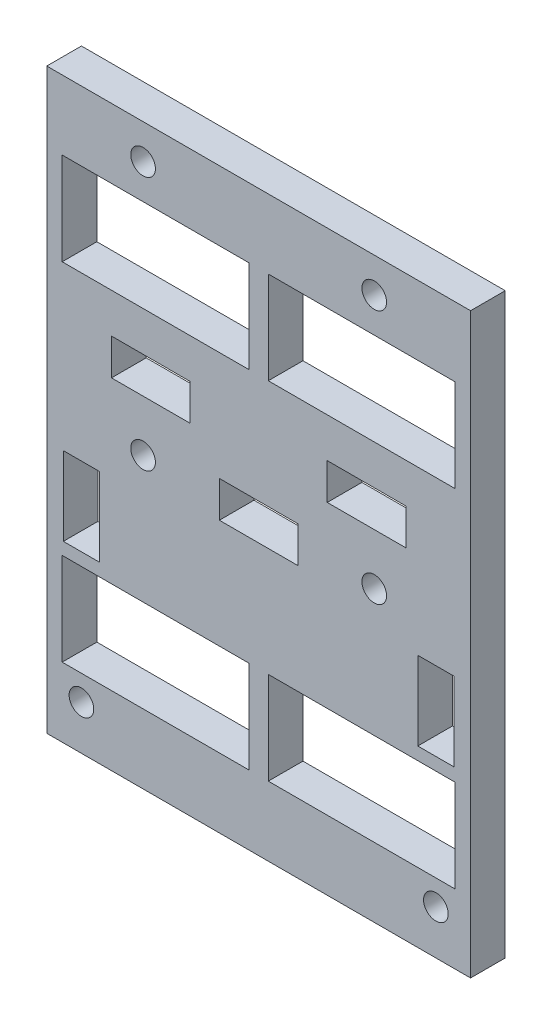
SolidWorks part; units mm, degrees
ref_plane "Front Plane" through (0, 0, 0) normal (0, 0, 1) x (1, 0, 0)
ref_plane "Top Plane" through (0, 0, 0) normal (0, 1, 0) x (1, 0, 0)
ref_plane "Right Plane" through (0, 0, 0) normal (1, 0, 0) x (0, 0, -1)
sketch "Sketch1" plane through (0, 0, 0) normal (0, 0, 1) x (1, 0, 0)
  line L0 (0, -37.5) -> (0, 37.5) construction
  line L1 (-27.5, -37.5) -> (27.5, -37.5)
  line L2 (-27.5, -37.5) -> (-27.5, 37.5)
  line L3 (-27.5, 37.5) -> (27.5, 37.5)
  line L4 (27.5, -37.5) -> (27.5, 37.5)
  line L5 (-27.5, -37.5) -> (27.5, 37.5) construction
  line L6 (-27.5, 37.5) -> (27.5, -37.5) construction
  line L7 (-27.5, 0) -> (27.5, 0) construction
  line L8 (-27.5, 22.5) -> (27.5, 22.5) construction
  line L9 (25.5, 16.5) -> (1.25, 28.5) construction
  line L10 (-25.5, 28.5) -> (-1.25, 28.5)
  line L11 (-25.5, 28.5) -> (-25.5, 16.5)
  line L12 (-25.5, 16.5) -> (-1.25, 16.5)
  line L13 (-1.25, 28.5) -> (-1.25, 16.5)
  line L14 (-25.5, 28.5) -> (-1.25, 16.5) construction
  line L15 (-25.5, 16.5) -> (-1.25, 28.5) construction
  line L16 (25.5, 28.5) -> (1.25, 16.5) construction
  line L17 (1.25, 28.5) -> (1.25, 16.5)
  line L18 (25.5, 16.5) -> (1.25, 16.5)
  line L19 (25.5, 28.5) -> (25.5, 16.5)
  line L20 (25.5, 28.5) -> (1.25, 28.5)
  line L21 (25.5, -28.5) -> (1.25, -16.5) construction
  line L22 (-25.5, -16.5) -> (-1.25, -28.5) construction
  line L23 (-25.5, -28.5) -> (-1.25, -16.5) construction
  line L24 (25.5, -16.5) -> (1.25, -28.5) construction
  line L25 (25.5, -28.5) -> (1.25, -28.5)
  line L26 (25.5, -28.5) -> (25.5, -16.5)
  line L27 (25.5, -16.5) -> (1.25, -16.5)
  line L28 (1.25, -28.5) -> (1.25, -16.5)
  line L29 (-1.25, -28.5) -> (-1.25, -16.5)
  line L30 (-25.5, -16.5) -> (-1.25, -16.5)
  line L31 (-25.5, -28.5) -> (-25.5, -16.5)
  line L32 (-25.5, -28.5) -> (-1.25, -28.5)
  point P0 (0, 0)
  point P12 (-13.375, 22.5)
  point P21 (13.375, 22.5)
  point P30 (13.375, -22.5)
  point P31 (-13.375, -22.5)
  dimension "D1" = 55
  dimension "D2" = 75
  dimension "D3" = 22.5
  dimension "D4" = 24.25
  dimension "D5" = 12
  dimension "D6" = 1.25
extrude "Boss-Extrude1" add sketch "Sketch1" along normal blind 4.5
sketch "Sketch2" plane through (0, 0, 4.5) normal (0, 0, 1) x (1, 0, 0)
  line L0 (0, -37.5) -> (0, 37.5) construction
  line L1 (-27.5, -37.5) -> (27.5, -37.5) construction
  line L2 (27.5, 37.5) -> (-27.5, 37.5) construction
  line L3 (-27.5, 0) -> (27.5, 0) construction
  line L4 (-27.5, 37.5) -> (-27.5, -37.5) construction
  line L5 (27.5, -37.5) -> (27.5, 37.5) construction
  line L6 (-15, 0) -> (15, 0) construction
  circle A0 centre (-15, 33) radius 1.6
  circle A1 centre (15, 33) radius 1.6
  circle A2 centre (15, 0) radius 1.6
  circle A3 centre (-15, 0) radius 1.6
  dimension "D1" = 3.2
  dimension "D7" = 3.2
  dimension "D8" = 3.2
  dimension "D2" = 15
  dimension "D3" = 33
  dimension "D4" = 30
  dimension "D5" = 15
  dimension "D6" = 0
extrude "screwHoles" cut sketch "Sketch2" against normal through all
sketch "Sketch3" plane through (0, 0, 4.5) normal (0, 0, 1) x (1, 0, 0)
  line L0 (-27.5, 9) -> (26.0486, 9) construction
  line L1 (-27.5, 37.5) -> (-27.5, -37.5) construction
  line L3 (0, 37.5) -> (0, -37.5) construction
  line L4 (27.5, 37.5) -> (-27.5, 37.5) construction
  line L5 (-27.5, -37.5) -> (27.5, -37.5) construction
  line L6 (19.1, 6.65) -> (8.9, 11.35) construction
  line L7 (-19.1, 11.35) -> (-8.9, 11.35)
  line L8 (-19.1, 11.35) -> (-19.1, 6.65)
  line L9 (-19.1, 6.65) -> (-8.9, 6.65)
  line L10 (-8.9, 11.35) -> (-8.9, 6.65)
  line L11 (-19.1, 11.35) -> (-8.9, 6.65) construction
  line L12 (-19.1, 6.65) -> (-8.9, 11.35) construction
  line L13 (19.1, 11.35) -> (8.9, 6.65) construction
  line L14 (8.9, 11.35) -> (8.9, 6.65)
  line L15 (19.1, 6.65) -> (8.9, 6.65)
  line L16 (19.1, 11.35) -> (19.1, 6.65)
  line L17 (19.1, 11.35) -> (8.9, 11.35)
  line L18 (-27.5, 37.5) -> (-27.5, -37.5) construction
  point P2 (-27.5, 0)
  point P12 (-14, 9)
  point P21 (14, 9)
  dimension "D1" = 10.2
  dimension "D2" = 4.7
  dimension "D3" = 14
  dimension "D4" = 9
extrude "BeltClamp" cut sketch "Sketch3" against normal through all
sketch "Sketch4" plane through (0, 0, 4.5) normal (0, 0, 1) x (1, 0, 0)
  line L0 (-27.5, 0) -> (27.5, 0) construction
  line L1 (-27.5, 37.5) -> (-27.5, -37.5) construction
  line L2 (27.5, -37.5) -> (27.5, 37.5) construction
  line L4 (-5.1, 2.35) -> (5.1, 2.35)
  line L5 (-5.1, 2.35) -> (-5.1, -2.35)
  line L6 (-5.1, -2.35) -> (5.1, -2.35)
  line L7 (5.1, 2.35) -> (5.1, -2.35)
  line L8 (-5.1, 2.35) -> (5.1, -2.35) construction
  line L9 (-5.1, -2.35) -> (5.1, 2.35) construction
  circle A0 centre (-15, 0) radius 1.6 construction
  point P6 (0, 0)
  dimension "D1" = 10.2
  dimension "D2" = 4.7
  dimension "D3" = 0
extrude "Cut-Extrude3" cut sketch "Sketch4" against normal through all
sketch "Sketch5" plane through (0, 0, 4.5) normal (0, 0, 1) x (1, 0, 0)
  line L0 (-27.5, -9.75) -> (27.5, -9.75) construction
  line L1 (-27.5, 37.5) -> (-27.5, -37.5) construction
  line L2 (27.5, -37.5) -> (27.5, 37.5) construction
  line L3 (5.1, -2.35) -> (5.1, 2.35) construction
  line L4 (0, -37.5) -> (0, 37.5) construction
  line L5 (-27.5, -37.5) -> (27.5, -37.5) construction
  line L6 (27.5, 37.5) -> (-27.5, 37.5) construction
  line L7 (-20.65, -14.85) -> (-25.35, -4.65) construction
  line L8 (20.65, -4.65) -> (25.35, -4.65)
  line L9 (20.65, -4.65) -> (20.65, -14.85)
  line L10 (20.65, -14.85) -> (25.35, -14.85)
  line L11 (25.35, -4.65) -> (25.35, -14.85)
  line L12 (20.65, -4.65) -> (25.35, -14.85) construction
  line L13 (20.65, -14.85) -> (25.35, -4.65) construction
  line L14 (-20.65, -4.65) -> (-25.35, -14.85) construction
  line L15 (-25.35, -4.65) -> (-25.35, -14.85)
  line L16 (-20.65, -14.85) -> (-25.35, -14.85)
  line L17 (-20.65, -4.65) -> (-20.65, -14.85)
  line L18 (-20.65, -4.65) -> (-25.35, -4.65)
  line L19 (23, -9.75) -> (23, -37.5) construction
  line L20 (-23, -9.75) -> (-23, -37.5) construction
  circle A0 centre (23, -31.75) radius 1.6
  circle A1 centre (-23, -31.75) radius 1.6
  point P6 (5.1, 0)
  point P15 (23, -9.75)
  point P24 (-23, -9.75)
  dimension "D5" = 3.2
  dimension "D1" = 9.75
  dimension "D2" = 10.2
  dimension "D3" = 4.7
  dimension "D4" = 23
  dimension "D6" = 22
extrude "Cut-Extrude4" cut sketch "Sketch5" against normal through all
sketch "Sketch6" plane through (0, 0, 4.5) normal (0, 0, 1) x (1, 0, 0)
  line L0 (-25.35, -9.75) -> (25.35, -9.75) construction
  line L1 (-25.35, -4.65) -> (-25.35, -14.85) construction
  line L2 (25.35, -14.85) -> (25.35, -4.65) construction
  line L3 (0, -2.35) -> (0, -37.5) construction
  line L4 (-5.1, -2.35) -> (5.1, -2.35) construction
  line L5 (-27.5, -37.5) -> (27.5, -37.5) construction
  line L6 (23, -14.85) -> (23, -4.65) construction
  line L7 (20.65, -14.85) -> (25.35, -14.85) construction
  line L8 (25.35, -4.65) -> (20.65, -4.65) construction
  line L9 (20.65, -4.65) -> (20.65, -14.85) construction
  line L10 (19.65, -15.85) -> (26.35, -15.85)
  line L11 (19.65, -15.85) -> (19.65, -3.65)
  line L12 (19.65, -3.65) -> (26.35, -3.65)
  line L13 (26.35, -15.85) -> (26.35, -3.65)
  line L14 (19.65, -15.85) -> (26.35, -3.65) construction
  line L15 (19.65, -3.65) -> (26.35, -15.85) construction
  line L16 (-19.65, -3.65) -> (-26.35, -15.85) construction
  line L17 (-19.65, -15.85) -> (-26.35, -3.65) construction
  line L18 (-23, -14.85) -> (-23, -4.65) construction
  line L19 (-26.35, -15.85) -> (-26.35, -3.65)
  line L20 (-19.65, -3.65) -> (-26.35, -3.65)
  line L21 (-19.65, -15.85) -> (-19.65, -3.65)
  line L22 (-19.65, -15.85) -> (-26.35, -15.85)
  circle A0 centre (23, -9.75) radius 1.6
  circle A1 centre (-23, -9.75) radius 1.6
  point P18 (23, -9.75)
  dimension "D3" = 3.2
  dimension "D1" = 1
  dimension "D2" = 1
extrude "FrontToRear1" [suppressed] add sketch "Sketch6" against normal up to surface (4.5 mm away) up to face at (-24.6, -31.75, 0)
sketch "Sketch7" plane through (0, 0, 4.5) normal (0, 0, 1) x (1, 0, 0)
  line L0 (5.1, 2.35) -> (-5.1, 2.35) construction
  line L1 (-20, -3.35) -> (20, -3.35)
  line L2 (-20, -3.35) -> (-20, 3.35)
  line L3 (-20, 3.35) -> (20, 3.35)
  line L4 (20, -3.35) -> (20, 3.35)
  line L5 (-20, -3.35) -> (20, 3.35) construction
  line L6 (-20, 3.35) -> (20, -3.35) construction
  circle A0 centre (15, 0) radius 1.6 construction
  point P0 (0, 0)
  dimension "D1" = 1
  dimension "D2" = 5
extrude "FrontToRear2" [suppressed] add sketch "Sketch7" against normal through all
equation "\"X-ROD-SPACING\"=45"
equation "\"Y-ROD-SPACING\"=75"
equation "\"Z-ROD-SPACING\"=17.5"
equation "\"Y-BED-OFFSET\"=2"
equation "\"Y-BED-ROD-INSET\"=3.5"
equation "\"Y-BED-SCREW-SPACING\"=209"
equation "\"Y-BED-SCREW-CUTOUT-SLOT-HEIGHT\"=1"
equation "\"T-SLOT-NUT-FILLET-RADIUS\"=0.25"
equation "\"T-SLOT-SCREW-SHAFT-RADIUS\"=1.75"
equation "\"T-SLOT-SCREW-SHAFT-CUTOUT-LENGTH\"=10.5"
equation "\"T-SLOT-NUT-DEPTH\"=4.2"
equation "\"T-SLOT-NUT-WIDTH\"=3"
equation "\"T-SLOT-NUT-END-DISTANCE\"=8"
equation "\"ACRYLIC-THICKNESS\"=10"
equation "\"ACRYLIC-THICKNESS2\"=4.5"
equation "\"ACRYLIC-TAB-CUTOUT-SIZE\"=\"ACRYLIC-THICKNESS\"+\"ACRYLIC-TAB-TOLERANCE\"*2"
equation "\"ACRYLIC-TAB-WIDTH\"=\"ACRYLIC-THICKNESS\""
equation "\"ACRYLIC-M3-HOLE\"=3.2"
equation "\"SMOOTHROD-CAP-SCREW-DISTANCE\"=20"
equation "\"FRAME-WIDTH-INNER\"=370"
equation "\"NEMA17-HOLE-SPACING\"=31"
equation "\"NEMA17-CENTRAL-CUTOUT\"=22.5"
equation "\"Z-BRACKET-REACH\"=55"
equation "\"Z-ROD-INSET\"=16"
equation "\"TOP-BRACKET-SPACING\"=40"
equation "\"SMOOTHROD-X-LENGTH\"=350"
equation "\"SMOOTHROD-Y-LENGTH\"=350"
equation "\"SMOOTHROD-Z-LENGTH\"=350"
equation "\"SMOOTHROD-TIGHTENING-HEADROOM\"=1"
equation "\"LEADSCREW-Z-LENGTH\"=300"
equation "\"SCREW-LENGTH-FRAME\"=\"ACRYLIC-THICKNESS\" + 10"
equation "\"SCREW-LENGTH-MOTOR\"=\"ACRYLIC-THICKNESS\" + 5"
equation "\"SCREW-HEAD-RADIUS\"=6"
equation "\"PRINTED-X-SMOOTHROD-DIAMETER\"=8.2"
equation "\"PRINTED-X-SMOOTHROD-CUTOUT\"=10"
equation "\"PRINTED-X-BASE-HEIGHT\"=10"
equation "\"PRINTED-LM8UU-CUTOUT-SIZE\"=15.25"
equation "\"PRINTED-LM8UU-CUTOUT-LENGTH\"=24.5"
equation "\"PRINTED-X-IDLER-HEIGHT\"=16"
equation "\"PSU-MOUNTING-WIDTH\"=95"
equation "\"PSU-MOUNTING-HEIGHT\"=177"
equation "\"Y-BELT-TO-ROD-DISTANCE\"=20"
equation "\"SPOOL-HOLDER-ROD-SPACING\"=150"
equation "\"D3@Sketch1\"=\"X-ROD-SPACING\"/2"
equation "\"D4@Sketch1\"=\"ACRYLIC-X-CARRIAGE-LM8UU-CUTOUT-WIDTH\""
equation "\"D1@Boss-Extrude1\"=\"ACRYLIC-THICKNESS2\""
equation "\"D1@Sketch2\"=\"ACRYLIC-M3-HOLE\""
equation "\"D1@Sketch3\"=\"ACRYLIC-TAB-CUTOUT-SIZE\""
equation "\"D2@Sketch3\"=\"ACRYLIC-THICKNESS2\"+\"ACRYLIC-TAB-TOLERANCE\"*2"
equation "\"ACRYLIC-X-CARRIAGE-WIDTH\"=55"
equation "\"ACRYLIC-X-CARRIAGE-HEIGHT\"=75"
equation "\"D1@Sketch1\"=\"ACRYLIC-X-CARRIAGE-WIDTH\""
equation "\"D2@Sketch1\"=\"ACRYLIC-X-CARRIAGE-HEIGHT\""
equation "\"ACRYLIC-X-CARRIAGE-CENTER-TAB-SPACING\"=14"
equation "\"D3@Sketch3\"=\"ACRYLIC-X-CARRIAGE-CENTER-TAB-SPACING\""
equation "\"SCREW-LENGTH-EXTRUDER\"=28"
equation "\"ACRYLIC-X-CARRIAGE-SCREW-SPACING-X\"=15"
equation "\"ACRYLIC-X-CARRIAGE-SCREW-SPACING-Y\"=33"
equation "\"D2@Sketch2\"=\"ACRYLIC-X-CARRIAGE-SCREW-SPACING-X\""
equation "\"D3@Sketch2\"=\"ACRYLIC-X-CARRIAGE-SCREW-SPACING-Y\""
equation "\"D1@Sketch4\"=\"ACRYLIC-TAB-CUTOUT-SIZE\""
equation "\"D2@Sketch4\"=\"ACRYLIC-THICKNESS2\"+\"ACRYLIC-TAB-TOLERANCE\"*2"
equation "\"D2@Sketch5\"=\"ACRYLIC-TAB-CUTOUT-SIZE\""
equation "\"D3@Sketch5\"=\"ACRYLIC-THICKNESS2\"+\"ACRYLIC-TAB-TOLERANCE\"*2"
equation "\"ACRYLIC-X-CARRIAGE-EXTRUDER-SHELF-DEPTH\"=\"ACRYLIC-X-CARRIAGE-EXTRUDER-OFFSET\" + 30"
equation "\"ACRYLIC-X-CARRIAGE-EXTRUDER-BRACE-SPACING\"=23"
equation "\"D4@Sketch5\"=\"ACRYLIC-X-CARRIAGE-EXTRUDER-BRACE-SPACING\""
equation "\"D1@Sketch5\"=\"ACRYLIC-THICKNESS2\"/2 + 7.5"
equation "\"D4@Sketch2\"=\"ACRYLIC-X-CARRIAGE-SCREW-SPACING-X\"*2"
equation "\"D5@Sketch2\"=\"ACRYLIC-X-CARRIAGE-SCREW-SPACING-X\""
equation "\"D7@Sketch2\"=\"ACRYLIC-M3-HOLE\""
equation "\"D8@Sketch2\"=\"ACRYLIC-M3-HOLE\""
equation "\"ACRYLIC-X-CARRIAGE-LM8UU-CUTOUT-WIDTH\"=24.25"
equation "\"ACRYLIC-TAB-TOLERANCE\"=.1"
equation "\"ACRYLIC-X-CARRIAGE-EXTRUDER-OFFSET\"=26"
equation "\"ACRYLIC-X-CARRIAGE-EXTRUDER-ANGLE\"=90"
equation "\"ACRYLIC-X-CARRIAGE-EXTRUDER-BRACE-TAB-OFFSET\"=20"
equation "\"ACRYLIC-X-CARRIAGE-EXTRUDER-BRACE-HEIGHT\"=35"
equation "\"ACRYLIC-X-CARRIAGE-EXTRUDER-BRACE-SCREW-SPACING\"=22"
equation "\"D5@Sketch5\"=\"ACRYLIC-M3-HOLE\""
equation "\"D3@Sketch6\"=\"ACRYLIC-M3-HOLE\""
equation "\"ACRYLIC-X-CARRIAGE-LM8UU-CUTOUT-HEIGHT\"=12"
equation "\"ACRYLIC-X-CARRIAGE-DUAL-WIDTH-MULTIPLIER\"=1.65"
equation "\"ACRYLIC-X-CARRIAGE-DUAL-HOTEND-SPACING\"=42"
equation "\"ACRYLIC-X-CARRIAGE-DUAL-WIDTH\"=103"
equation "\"ACRYLIC-X-CARRIAGE-DUAL-HOTEND-SEPARATION\"=35"
equation "\"ACRYLIC-X-CARRIAGE-DUAL-MOUNT-PLATE-DEPTH\"=76"
equation "\"ACRYLIC-X-CARRIAGE-DUAL-MOUNT-BRACE-WIDTH\"=45"
equation "\"ACRYLIC-X-CARRIAGE-DUAL-MOUNT-SCREW-WIDTH\"=40"
equation "\"D5@Sketch1\"=\"ACRYLIC-X-CARRIAGE-LM8UU-CUTOUT-HEIGHT\""
